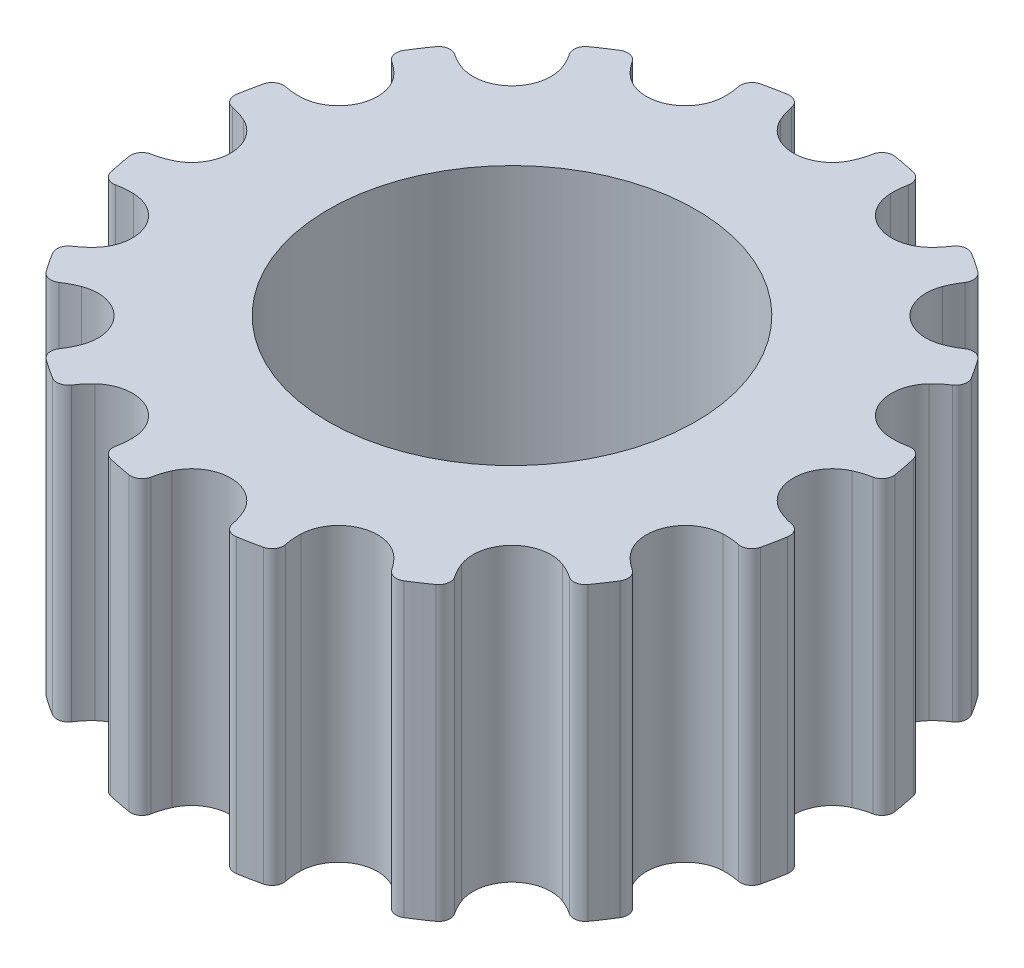
SolidWorks part; units mm, degrees
material "Alum Plate"
ref_plane "Front Plane" through (0, 0, 0) normal (0, 0, 1) x (1, 0, 0)
ref_plane "Top Plane" through (0, 0, 0) normal (0, 1, 0) x (1, 0, 0)
ref_plane "Right Plane" through (0, 0, 0) normal (1, 0, 0) x (0, 0, -1)
other "Bounding Box"
ref_plane "Default Plane" through (-8.9266, -12.7485, 0) normal (-0.1736, 0.9848, 0) x (0.9848, 0.1736, 0)
sketch "Sketch1" plane through (0, 0, 0) normal (0, 1, 0) x (1, 0, 0)
  line L0 (0, -7.8245) -> (0, 0) construction
  circle A0 centre (0, 0) radius 4
  arc B0 (-1.8508, -6.777) -> (-1.6633, -7.0715) centre (-1.6061, -6.8282) ccw
  arc B1 (-1.6633, -7.0715) -> (-1.1695, -7.1697) centre (0, 0) ccw
  arc B2 (-1.1695, -7.1697) -> (-0.8836, -6.9694) centre (-1.1292, -6.923) ccw
  arc B3 (-0.7739, -6.6229) -> (-0.8836, -6.9694) centre (0.61, -7.2516) ccw
  arc B4 (0.7739, -6.6229) -> (-0.7739, -6.6229) centre (0, -6.9745) ccw
  arc B5 (0.8836, -6.9694) -> (0.7739, -6.6229) centre (-0.61, -7.2516) ccw
  arc B6 (0.8836, -6.9694) -> (1.1695, -7.1697) centre (1.1292, -6.923) ccw
  arc B7 (1.1695, -7.1697) -> (1.6633, -7.0715) centre (0, 0) ccw
  arc B8 (1.6633, -7.0715) -> (1.8508, -6.777) centre (1.6061, -6.8282) ccw
  arc B9 (1.8195, -6.4149) -> (1.8508, -6.777) centre (3.3386, -6.4662) ccw
  arc B10 (3.2495, -5.8226) -> (1.8195, -6.4149) centre (2.669, -6.4436) ccw
  arc B11 (3.4834, -6.1008) -> (3.2495, -5.8226) centre (2.2115, -6.9331) ccw
  arc B12 (3.4834, -6.1008) -> (3.8242, -6.1764) centre (3.6926, -5.9639) ccw
  arc B13 (3.8242, -6.1764) -> (4.2428, -5.8967) centre (0, 0) ccw
  arc B14 (4.2428, -5.8967) -> (4.3033, -5.5529) centre (4.0968, -5.6938) ccw
  arc B15 (4.1359, -5.2303) -> (4.3033, -5.5529) centre (5.559, -4.6963) ccw
  arc B16 (5.2303, -4.1359) -> (4.1359, -5.2303) centre (4.9317, -4.9317) ccw
  arc B17 (5.5529, -4.3033) -> (5.2303, -4.1359) centre (4.6963, -5.559) ccw
  arc B18 (5.5529, -4.3033) -> (5.8967, -4.2428) centre (5.6938, -4.0968) ccw
  arc B19 (5.8967, -4.2428) -> (6.1764, -3.8242) centre (0, 0) ccw
  arc B20 (6.1764, -3.8242) -> (6.1008, -3.4834) centre (5.9639, -3.6926) ccw
  arc B21 (5.8226, -3.2495) -> (6.1008, -3.4834) centre (6.9331, -2.2115) ccw
  arc B22 (6.4149, -1.8195) -> (5.8226, -3.2495) centre (6.4436, -2.669) ccw
  arc B23 (6.777, -1.8508) -> (6.4149, -1.8195) centre (6.4662, -3.3386) ccw
  arc B24 (6.777, -1.8508) -> (7.0715, -1.6633) centre (6.8282, -1.6061) ccw
  arc B25 (7.0715, -1.6633) -> (7.1697, -1.1695) centre (0, 0) ccw
  arc B26 (7.1697, -1.1695) -> (6.9694, -0.8836) centre (6.923, -1.1292) ccw
  arc B27 (6.6229, -0.7739) -> (6.9694, -0.8836) centre (7.2516, 0.61) ccw
  arc B28 (6.6229, 0.7739) -> (6.6229, -0.7739) centre (6.9745, 0) ccw
  arc B29 (6.9694, 0.8836) -> (6.6229, 0.7739) centre (7.2516, -0.61) ccw
  arc B30 (6.9694, 0.8836) -> (7.1697, 1.1695) centre (6.923, 1.1292) ccw
  arc B31 (7.1697, 1.1695) -> (7.0715, 1.6633) centre (0, 0) ccw
  arc B32 (7.0715, 1.6633) -> (6.777, 1.8508) centre (6.8282, 1.6061) ccw
  arc B33 (6.4149, 1.8195) -> (6.777, 1.8508) centre (6.4662, 3.3386) ccw
  arc B34 (5.8226, 3.2495) -> (6.4149, 1.8195) centre (6.4436, 2.669) ccw
  arc B35 (6.1008, 3.4834) -> (5.8226, 3.2495) centre (6.9331, 2.2115) ccw
  arc B36 (6.1008, 3.4834) -> (6.1764, 3.8242) centre (5.9639, 3.6926) ccw
  arc B37 (6.1764, 3.8242) -> (5.8967, 4.2428) centre (0, 0) ccw
  arc B38 (5.8967, 4.2428) -> (5.5529, 4.3033) centre (5.6938, 4.0968) ccw
  arc B39 (5.2303, 4.1359) -> (5.5529, 4.3033) centre (4.6963, 5.559) ccw
  arc B40 (4.1359, 5.2303) -> (5.2303, 4.1359) centre (4.9317, 4.9317) ccw
  arc B41 (4.3033, 5.5529) -> (4.1359, 5.2303) centre (5.559, 4.6963) ccw
  arc B42 (4.3033, 5.5529) -> (4.2428, 5.8967) centre (4.0968, 5.6938) ccw
  arc B43 (4.2428, 5.8967) -> (3.8242, 6.1764) centre (0, 0) ccw
  arc B44 (3.8242, 6.1764) -> (3.4834, 6.1008) centre (3.6926, 5.9639) ccw
  arc B45 (3.2495, 5.8226) -> (3.4834, 6.1008) centre (2.2115, 6.9331) ccw
  arc B46 (1.8195, 6.4149) -> (3.2495, 5.8226) centre (2.669, 6.4436) ccw
  arc B47 (1.8508, 6.777) -> (1.8195, 6.4149) centre (3.3386, 6.4662) ccw
  arc B48 (1.8508, 6.777) -> (1.6633, 7.0715) centre (1.6061, 6.8282) ccw
  arc B49 (1.6633, 7.0715) -> (1.1695, 7.1697) centre (0, 0) ccw
  arc B50 (1.1695, 7.1697) -> (0.8836, 6.9694) centre (1.1292, 6.923) ccw
  arc B51 (0.7739, 6.6229) -> (0.8836, 6.9694) centre (-0.61, 7.2516) ccw
  arc B52 (-0.7739, 6.6229) -> (0.7739, 6.6229) centre (0, 6.9745) ccw
  arc B53 (-0.8836, 6.9694) -> (-0.7739, 6.6229) centre (0.61, 7.2516) ccw
  arc B54 (-0.8836, 6.9694) -> (-1.1695, 7.1697) centre (-1.1292, 6.923) ccw
  arc B55 (-1.1695, 7.1697) -> (-1.6633, 7.0715) centre (0, 0) ccw
  arc B56 (-1.6633, 7.0715) -> (-1.8508, 6.777) centre (-1.6061, 6.8282) ccw
  arc B57 (-1.8195, 6.4149) -> (-1.8508, 6.777) centre (-3.3386, 6.4662) ccw
  arc B58 (-3.2495, 5.8226) -> (-1.8195, 6.4149) centre (-2.669, 6.4436) ccw
  arc B59 (-3.4834, 6.1008) -> (-3.2495, 5.8226) centre (-2.2115, 6.9331) ccw
  arc B60 (-3.4834, 6.1008) -> (-3.8242, 6.1764) centre (-3.6926, 5.9639) ccw
  arc B61 (-3.8242, 6.1764) -> (-4.2428, 5.8967) centre (0, 0) ccw
  arc B62 (-4.2428, 5.8967) -> (-4.3033, 5.5529) centre (-4.0968, 5.6938) ccw
  arc B63 (-4.1359, 5.2303) -> (-4.3033, 5.5529) centre (-5.559, 4.6963) ccw
  arc B64 (-5.2303, 4.1359) -> (-4.1359, 5.2303) centre (-4.9317, 4.9317) ccw
  arc B65 (-5.5529, 4.3033) -> (-5.2303, 4.1359) centre (-4.6963, 5.559) ccw
  arc B66 (-5.5529, 4.3033) -> (-5.8967, 4.2428) centre (-5.6938, 4.0968) ccw
  arc B67 (-5.8967, 4.2428) -> (-6.1764, 3.8242) centre (0, 0) ccw
  arc B68 (-6.1764, 3.8242) -> (-6.1008, 3.4834) centre (-5.9639, 3.6926) ccw
  arc B69 (-5.8226, 3.2495) -> (-6.1008, 3.4834) centre (-6.9331, 2.2115) ccw
  arc B70 (-6.4149, 1.8195) -> (-5.8226, 3.2495) centre (-6.4436, 2.669) ccw
  arc B71 (-6.777, 1.8508) -> (-6.4149, 1.8195) centre (-6.4662, 3.3386) ccw
  arc B72 (-6.777, 1.8508) -> (-7.0715, 1.6633) centre (-6.8282, 1.6061) ccw
  arc B73 (-7.0715, 1.6633) -> (-7.1697, 1.1695) centre (0, 0) ccw
  arc B74 (-7.1697, 1.1695) -> (-6.9694, 0.8836) centre (-6.923, 1.1292) ccw
  arc B75 (-6.6229, 0.7739) -> (-6.9694, 0.8836) centre (-7.2516, -0.61) ccw
  arc B76 (-6.6229, -0.7739) -> (-6.6229, 0.7739) centre (-6.9745, 0) ccw
  arc B77 (-6.9694, -0.8836) -> (-6.6229, -0.7739) centre (-7.2516, 0.61) ccw
  arc B78 (-6.9694, -0.8836) -> (-7.1697, -1.1695) centre (-6.923, -1.1292) ccw
  arc B79 (-7.1697, -1.1695) -> (-7.0715, -1.6633) centre (0, 0) ccw
  arc B80 (-7.0715, -1.6633) -> (-6.777, -1.8508) centre (-6.8282, -1.6061) ccw
  arc B81 (-6.4149, -1.8195) -> (-6.777, -1.8508) centre (-6.4662, -3.3386) ccw
  arc B82 (-5.8226, -3.2495) -> (-6.4149, -1.8195) centre (-6.4436, -2.669) ccw
  arc B83 (-6.1008, -3.4834) -> (-5.8226, -3.2495) centre (-6.9331, -2.2115) ccw
  arc B84 (-6.1008, -3.4834) -> (-6.1764, -3.8242) centre (-5.9639, -3.6926) ccw
  arc B85 (-6.1764, -3.8242) -> (-5.8967, -4.2428) centre (0, 0) ccw
  arc B86 (-5.8967, -4.2428) -> (-5.5529, -4.3033) centre (-5.6938, -4.0968) ccw
  arc B87 (-5.2303, -4.1359) -> (-5.5529, -4.3033) centre (-4.6963, -5.559) ccw
  arc B88 (-4.1359, -5.2303) -> (-5.2303, -4.1359) centre (-4.9317, -4.9317) ccw
  arc B89 (-4.3033, -5.5529) -> (-4.1359, -5.2303) centre (-5.559, -4.6963) ccw
  arc B90 (-4.3033, -5.5529) -> (-4.2428, -5.8967) centre (-4.0968, -5.6938) ccw
  arc B91 (-4.2428, -5.8967) -> (-3.8242, -6.1764) centre (0, 0) ccw
  arc B92 (-3.8242, -6.1764) -> (-3.4834, -6.1008) centre (-3.6926, -5.9639) ccw
  arc B93 (-3.2495, -5.8226) -> (-3.4834, -6.1008) centre (-2.2115, -6.9331) ccw
  arc B94 (-1.8195, -6.4149) -> (-3.2495, -5.8226) centre (-2.669, -6.4436) ccw
  arc B95 (-1.8508, -6.777) -> (-1.8195, -6.4149) centre (-3.3386, -6.4662) ccw
  dimension "D1" = 8
sketch_block_instance "Block-GT2 16 Tooth Profile-1"
sketch_block "Block-GT2 16 Tooth Profile"
extrude "Boss-Extrude1" add sketch "Sketch1" along normal mid plane 6.35
